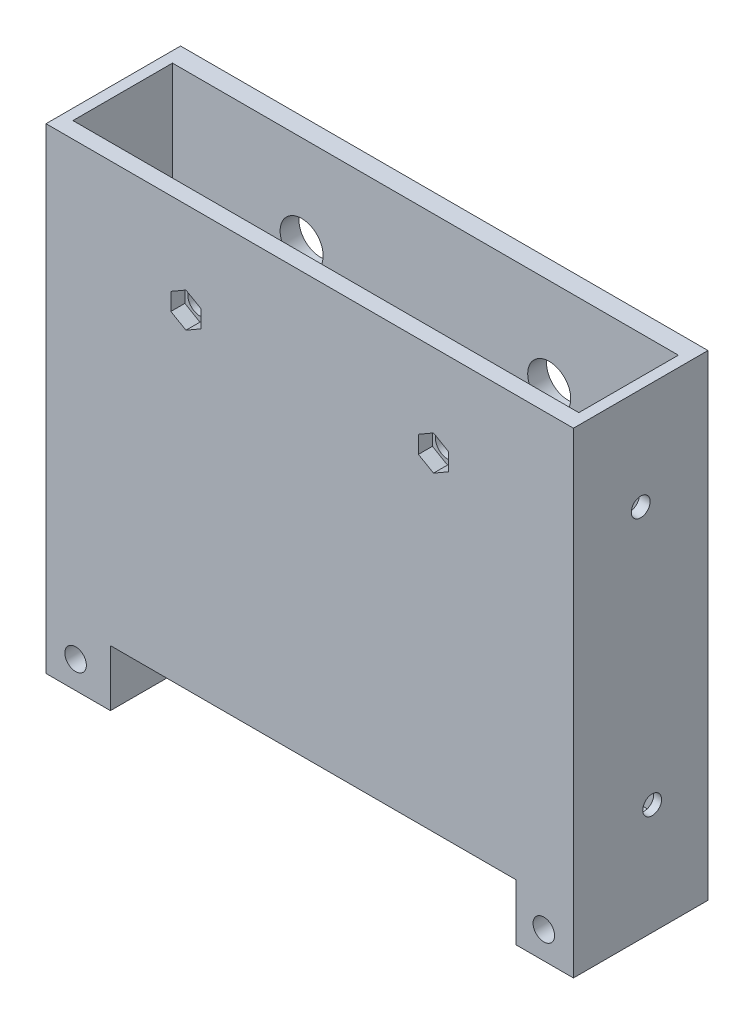
SolidWorks part; units mm, degrees
ref_plane "Front" through (0, 0, 0) normal (0, 0, 1) x (1, 0, 0)
ref_plane "Top" through (0, 0, 0) normal (0, 1, 0) x (1, 0, 0)
ref_plane "Right" through (0, 0, 0) normal (1, 0, 0) x (0, 0, -1)
sketch "草图2" plane through (0, 0, 0) normal (0, 0, 1) x (1, 0, 0)
  line L0 (-46.6651, 43.9646) -> (-46.6651, -34.0354)
  line L1 (-42.6651, 39.9646) -> (47.3349, 39.9646) construction
  line L2 (-42.6651, 39.9646) -> (-42.6651, -30.0354) construction
  line L3 (-42.6651, -30.0354) -> (47.3349, -30.0354) construction
  line L4 (47.3349, 39.9646) -> (47.3349, -30.0354) construction
  line L5 (-46.6651, -34.0354) -> (51.3349, -34.0354)
  line L6 (51.3349, 43.9646) -> (51.3349, -34.0354)
  line L7 (-46.6651, 43.9646) -> (51.3349, 43.9646)
  circle A0 centre (-20.6651, 26.9646) radius 2.25
  circle A1 centre (25.3349, 26.9646) radius 2.25
  dimension "D7" = 4.5
  dimension "D8" = 4.5
  dimension "D1" = 90
  dimension "D2" = 70
  dimension "D3" = 57
  dimension "D4" = 57
  dimension "D5" = 22
  dimension "D6" = 22
  dimension "D9" = 4
extrude "凸台-拉伸1" add sketch "草图2" along normal blind 25
sketch "草图3" plane through (0, 0, 25) normal (0, 0, 1) x (1, 0, 0)
  line L1 (-44.6651, 39.9646) -> (49.3349, 39.9646)
  line L2 (-44.6651, 39.9646) -> (-44.6651, -30.0354)
  line L3 (-44.6651, -30.0354) -> (49.3349, -30.0354)
  line L4 (49.3349, 39.9646) -> (49.3349, -30.0354)
  line L5 (-44.6651, 0) -> (49.3349, 0) construction
  line L7 (2.3349, -34.0354) -> (2.3349, 43.9646) construction
  line L8 (-46.6651, -34.0354) -> (51.3349, -34.0354) construction
  line L9 (51.3349, 43.9646) -> (-46.6651, 43.9646) construction
  circle A0 centre (-20.6651, 26.9646) radius 2.25
  circle A1 centre (25.3349, 26.9646) radius 2.25
  point P8 (2.3349, 0)
  point P11 (2.3349, 0)
  point P12 (0, 0)
  point P21 (2.3349, 0)
  point P22 (0, 0)
  dimension "D7" = 4.5
  dimension "D8" = 4.5
  dimension "D1" = 94
  dimension "D2" = 70
  dimension "D3" = 57
  dimension "D4" = 57
sketch "草图4" plane through (0, -34.0354, 0) normal (0, -1, 0) x (1, 0, 0)
  line L1 (-44.3057, 17.15) -> (49.8763, 17.15)
  line L2 (-44.3057, 17.15) -> (-44.3057, 1.4638)
  line L3 (-44.3057, 1.4638) -> (49.8763, 1.4638)
  line L4 (49.8763, 17.15) -> (49.8763, 1.4638)
extrude "切除-拉伸1" cut sketch "草图4" against normal blind 15
extrude "切除-拉伸2" cut sketch "草图3" against normal blind 18.5 from offset 3 offset against normal yes
sketch "草图5" plane through (0, 0, 0) normal (0, 0, -1) x (-1, 0, 0)
  circle A0 centre (-25.3349, 26.9646) radius 4
  circle A1 centre (20.6651, 26.9646) radius 4
  dimension "D1" = 8
  dimension "D2" = 8
extrude "切除-拉伸3" cut sketch "草图5" against normal up to next
sketch "草图6" plane through (0, 0, 22) normal (0, 0, -1) x (-1, 0, 0)
  line L0 (-49.3349, -28.4771) -> (44.6651, -28.4771) construction
  line L1 (-49.3349, -30.0354) -> (-49.3349, 39.9646) construction
  line L2 (44.6651, 39.9646) -> (44.6651, -30.0354) construction
  line L3 (-2.3349, -28.4771) -> (-2.3349, -63.959) construction
  line L4 (-45.8349, -39.4492) -> (41.1651, -39.4492) construction
  line L5 (-51.3349, -34.0354) -> (-51.3349, 43.9646) construction
  line L6 (34.6982, -44.5083) -> (46.6651, -44.5083)
  line L7 (34.6982, -44.5083) -> (34.6982, -34.0354)
  line L8 (34.6982, -34.0354) -> (46.6651, -34.0354)
  line L9 (46.6651, -44.5083) -> (46.6651, -34.0354)
  line L10 (-51.3349, -33.9719) -> (-40.6193, -33.9719)
  line L11 (-51.3349, -33.9719) -> (-51.3349, -44.5083)
  line L12 (-51.3349, -44.5083) -> (-40.6193, -44.5083)
  line L13 (-40.6193, -33.9719) -> (-40.6193, -44.5083)
  line L14 (46.6651, -34.0354) -> (-51.3349, -34.0354) construction
  line L16 (46.6651, 43.9646) -> (46.6651, -34.0354) construction
  circle A0 centre (41.1651, -39.4492) radius 2
  circle A2 centre (-45.8349, -39.4492) radius 2
  point P14 (-2.3349, -39.4492)
  point P25 (0, 0)
  point P26 (41.1651, -40.3141)
  point P27 (-45.9771, -40.6775)
  point P28 (-45.8349, -39.4492)
  dimension "D2" = 4
  dimension "D3" = 4
  dimension "D1" = 87
extrude "凸台-拉伸3" add sketch "草图6" along normal through all and the other way through all
sketch "草图7" plane through (0, 0, 0) normal (0, 0, -1) x (-1, 0, 0)
  circle A0 centre (-45.8349, -39.4492) radius 3
  circle A1 centre (41.1651, -39.4492) radius 3
  point P6 (-45.8349, -36.7188)
  point P7 (0, 0)
  point P8 (-45.8349, -39.4492)
  dimension "D1" = 6
  dimension "D2" = 6
extrude "切除-拉伸4" cut sketch "草图7" against normal blind 15
sketch "草图9" plane through (0, 39.9646, 0) normal (0, -1, 0) x (1, 0, 0)
  line L1 (-44.6651, 3.5) -> (49.3349, 3.5)
  line L2 (-44.6651, 3.5) -> (-44.6651, 22)
  line L3 (-44.6651, 22) -> (49.3349, 22)
  line L4 (49.3349, 3.5) -> (49.3349, 22)
extrude "切除-拉伸5" cut sketch "草图9" against normal blind 15
sketch "草图10" plane through (0, 0, 22) normal (0, 0, -1) x (-1, 0, 0)
  circle A0 centre (-25.3349, 26.9646) radius 4
  circle A1 centre (20.6651, 26.9646) radius 4
  circle A2 centre (20.6651, 26.9646) radius 2.25
  circle A3 centre (-25.3349, 26.9646) radius 2.25
  dimension "D1" = 8
  dimension "D2" = 8
extrude "凸台-拉伸4" add sketch "草图10" along normal blind 2.5
fillet "圆角1" radius 10 2 edges at (-16.6651, 26.9646, 22) (29.3349, 26.9646, 22)
sketch "草图12" plane through (-46.6651, 0, 0) normal (-1, 0, 0) x (0, 0, 1)
  line L0 (0, -23.9466) -> (25, -23.9466) construction
  line L1 (0, 43.9646) -> (0, -44.5083) construction
  line L2 (25, 43.9646) -> (25, -44.5083) construction
  line L3 (0, 25.0534) -> (25, 25.0534) construction
  circle A0 centre (10.3727, -23.9466) radius 1.75
  circle A1 centre (12.5, 25.0534) radius 1.75
  dimension "D1" = 3.5
  dimension "D2" = 3.5
  dimension "D3" = 49
extrude "切除-拉伸6" cut sketch "草图12" against normal through all
sketch "草图13" plane through (0, 0, 25) normal (0, 0, 1) x (1, 0, 0)
  line L1 (-20.6651, 30.1978) -> (-23.4651, 28.5812)
  line L2 (-23.4651, 28.5812) -> (-23.4651, 25.348)
  line L3 (-23.4651, 25.348) -> (-20.6651, 23.7315)
  line L4 (-20.6651, 23.7315) -> (-17.8651, 25.348)
  line L5 (-17.8651, 25.348) -> (-17.8651, 28.5812)
  line L6 (-17.8651, 28.5812) -> (-20.6651, 30.1978)
  line L7 (25.3349, 30.1978) -> (22.5349, 28.5812)
  line L8 (22.5349, 28.5812) -> (22.5349, 25.348)
  line L9 (22.5349, 25.348) -> (25.3349, 23.7315)
  line L10 (25.3349, 23.7315) -> (28.1349, 25.348)
  line L11 (28.1349, 25.348) -> (28.1349, 28.5812)
  line L12 (28.1349, 28.5812) -> (25.3349, 30.1978)
  circle A0 centre (-20.6651, 26.9646) radius 2.8 construction
  circle A1 centre (25.3349, 26.9646) radius 2.8 construction
  dimension "D1" = 5.6
  dimension "D2" = 5.6
extrude "切除-拉伸7" cut sketch "草图13" against normal blind 2.6
